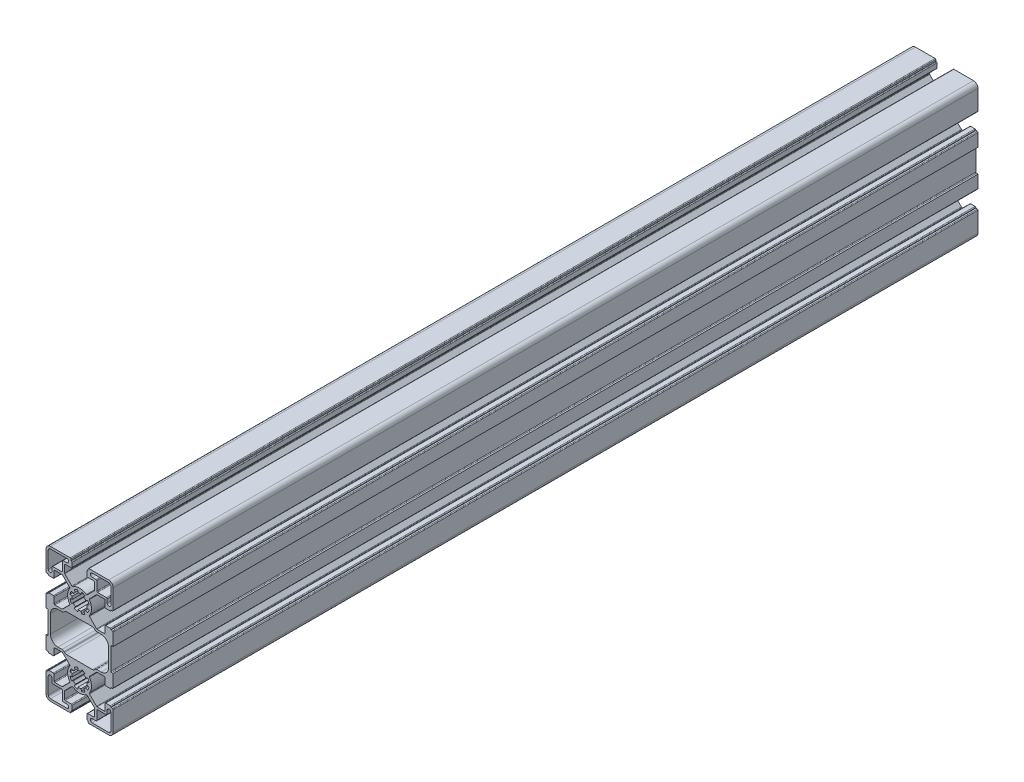
SolidWorks part; units mm, degrees
ref_plane "Front Plane" through (0, 0, 0) normal (0, 0, 1) x (1, 0, 0)
ref_plane "Top Plane" through (0, 0, 0) normal (0, 1, 0) x (1, 0, 0)
ref_plane "Right Plane" through (0, 0, 0) normal (1, 0, 0) x (0, 0, -1)
sketch "Sketch1" plane through (0, 0, 0) normal (0, 0, 1) x (1, 0, 0)
  line L0 (0, 45) -> (0, 0) construction
  line L1 (22.5, 22.5) -> (-22.5, 22.5) construction
  line L2 (-5.8, 45) -> (5.8, 45) construction
  line L3 (-5, 43.5) -> (5, 43.5) construction
  line L4 (-10.05, 32.55) -> (10.05, 32.55) construction
  line L5 (0, 22.5) -> (-10.05, 32.55) construction
  line L6 (0, 0) -> (0, -45) construction
  circle A0 centre (0, 22.5) radius 5 construction
  point P4 (0, 0)
  point P8 (0, 22.5)
  point P10 (0, 30.5)
  point P14 (0, 45)
  point P17 (0, 43.5)
  point P19 (0, 32.55)
  dimension "Center Hole Diameter" = 10
  dimension "T-Slot Depth" = 14.5
  dimension "T-Slot Width 2" = 11.6
  dimension "T-Slot Width" = 10
  dimension "Wall" = 1.5
  dimension "T-Slot Max Width" = 20.1
  dimension "Rail Width" = 45
  dimension "Rail Height" = 90
sketch "Sketch2" plane through (0, 0, 0) normal (1, 0, 0) x (0, 0, -1)
  line L0 (152.4, 0) -> (-152.4, 0) construction
  point P4 (0, 0)
  dimension "Length" = 304.8
sketch "Sketch3" plane through (0, 0, 0) normal (0, 0, 1) x (1, 0, 0)
  line L5 (-21, 31.0375) -> (-21, 42)
  line L9 (0, 22.5) -> (-22.5, 45) construction
  line L10 (-11.55, 12.45) -> (-6.3569, 17.6431)
  line L11 (-19.5, 43.5) -> (-8.5375, 43.5)
  line L38 (-5.8, 45) -> (-5.8, 43.5)
  line L46 (-5.8, 43.5) -> (-5, 43.5)
  line L62 (-5, 43.5) -> (-5, 39.525)
  line L74 (-5, 39.525) -> (-10.05, 39.525)
  line L76 (-10.05, 39.525) -> (-10.05, 34.05)
  line L77 (-10.05, 34.05) -> (-4.8569, 28.8569)
  line L78 (-18.525, 31.0375) -> (-18.525, 34.05)
  line L79 (-10.05, 39.525) -> (-10.05, 45) construction
  line L80 (0, 45) -> (0, 0) construction
  line L81 (-5.8, 45) -> (5.8, 45) construction
  line L82 (10.05, 34.05) -> (4.8569, 28.8569)
  line L83 (10.05, 39.525) -> (10.05, 34.05)
  line L84 (5, 39.525) -> (10.05, 39.525)
  line L85 (5, 43.5) -> (5, 39.525)
  line L86 (5.8, 43.5) -> (5, 43.5)
  line L87 (5.8, 45) -> (5.8, 43.5)
  line L88 (-22.5, 16.7) -> (-21, 16.7)
  line L89 (-21, 16.7) -> (-21, 17.5)
  line L90 (-21, 17.5) -> (-17.025, 17.5)
  line L91 (-17.025, 17.5) -> (-17.025, 12.45)
  line L92 (-17.025, 12.45) -> (-11.55, 12.45)
  line L93 (-11.55, 12.45) -> (-6.3569, 17.6431)
  line L94 (-11.55, 32.55) -> (-6.3569, 27.3569)
  line L95 (-17.025, 32.55) -> (-11.55, 32.55)
  line L96 (-17.025, 27.5) -> (-17.025, 32.55)
  line L97 (-21, 27.5) -> (-17.025, 27.5)
  line L98 (-21, 28.3) -> (-21, 27.5)
  line L99 (-22.5, 28.3) -> (-21, 28.3)
  line L100 (-22.5, 28.3) -> (-22.5, 42)
  line L101 (-19.5, 45) -> (-5.8, 45)
  line L102 (-18.525, 34.05) -> (-11.55, 34.05)
  line L103 (-8.5375, 41.025) -> (-11.55, 41.025)
  line L104 (-11.55, 41.025) -> (-11.55, 34.05)
  line L108 (-22.5, 0) -> (22.5, 0) construction
  line L113 (-21, 0) -> (-19.5, 0)
  line L117 (5.8, 45) -> (19.5, 45)
  line L118 (22.5, 42) -> (22.5, 28.3)
  line L120 (0, 22.5) -> (22.5, 22.5) construction
  line L121 (-22.5, 7.8) -> (-22.5, 16.7)
  line L136 (-22.5, 7.8) -> (-21, 7.8)
  line L137 (-21, 7.8) -> (-21, 0)
  line L138 (21, 7.8) -> (21, 0)
  line L139 (22.5, 7.8) -> (21, 7.8)
  line L140 (8.6003, 12.45) -> (-8.6003, 12.45)
  line L141 (-10.0145, 11.8642) -> (-10.3429, 11.5358)
  line L142 (-11.7571, 10.95) -> (-14.5, 10.95)
  line L143 (-19.5, 5.95) -> (-19.5, 0)
  line L144 (10.0145, 11.8642) -> (10.3429, 11.5358)
  line L145 (11.7571, 10.95) -> (14.5, 10.95)
  line L146 (19.5, 5.95) -> (19.5, 0)
  line L147 (22.5, 28.3) -> (21, 28.3)
  line L148 (21, 28.3) -> (21, 27.5)
  line L149 (21, 27.5) -> (17.025, 27.5)
  line L150 (17.025, 27.5) -> (17.025, 32.55)
  line L151 (17.025, 32.55) -> (11.55, 32.55)
  line L152 (11.55, 32.55) -> (6.3569, 27.3569)
  line L153 (11.55, 12.45) -> (6.3569, 17.6431)
  line L154 (17.025, 12.45) -> (11.55, 12.45)
  line L155 (17.025, 17.5) -> (17.025, 12.45)
  line L156 (21, 17.5) -> (17.025, 17.5)
  line L157 (21, 16.7) -> (21, 17.5)
  line L158 (22.5, 16.7) -> (21, 16.7)
  line L159 (11.55, 12.45) -> (6.3569, 17.6431)
  line L160 (22.5, 16.7) -> (22.5, 7.8)
  line L161 (8.5375, 43.5) -> (19.5, 43.5)
  line L162 (21, 42) -> (21, 31.0375)
  line L163 (8.5375, 41.025) -> (11.55, 41.025)
  line L164 (11.55, 41.025) -> (11.55, 34.05)
  line L165 (18.525, 31.0375) -> (18.525, 34.05)
  line L166 (18.525, 34.05) -> (11.55, 34.05)
  line L179 (0, 22.5) -> (-11.55, 34.05) construction
  line L180 (0, 22.5) -> (11.55, 34.05) construction
  line L181 (-18.525, 13.9625) -> (-18.525, 10.95) [skipped]
  line L182 (-21, 3) -> (-21, 13.9625) [skipped]
  line L183 (-8.5375, 1.5) -> (-19.5, 1.5) [skipped]
  line L184 (-8.5375, 3.975) -> (-11.55, 3.975) [skipped]
  line L185 (-11.55, 3.975) -> (-11.55, 10.95) [skipped]
  line L186 (-18.525, 10.95) -> (-11.55, 10.95) [skipped]
  line L187 (19.5, 1.5) -> (8.5375, 1.5) [skipped]
  line L188 (8.5375, 3.975) -> (11.55, 3.975) [skipped]
  line L189 (11.55, 3.975) -> (11.55, 10.95) [skipped]
  line L190 (18.525, 10.95) -> (11.55, 10.95) [skipped]
  line L191 (18.525, 13.9625) -> (18.525, 10.95) [skipped]
  line L192 (21, 13.9625) -> (21, 3) [skipped]
  line L193 (19.5, 0) -> (21, 0)
  arc A2 (-21, 42) -> (-19.5, 43.5) centre (-19.5, 42) cw
  arc A73 (-4.8569, 28.8569) -> (4.8569, 28.8569) centre (0, 22.5) cw
  arc A74 (-6.3569, 27.3569) -> (-6.3569, 17.6431) centre (0, 22.5) ccw
  arc A75 (-19.5, 45) -> (-22.5, 42) centre (-19.5, 42) ccw
  arc A76 (-21, 31.0375) -> (-18.525, 31.0375) centre (-19.7625, 31.0375) ccw
  arc A77 (-8.5375, 43.5) -> (-8.5375, 41.025) centre (-8.5375, 42.2625) cw
  arc A80 (19.5, 45) -> (22.5, 42) centre (19.5, 42) cw
  circle A88 centre (0, 22.5) radius 5 construction
  circle A89 centre (0, 22.5) radius 5
  arc A90 (-14.5, 10.95) -> (-19.5, 5.95) centre (-14.5, 5.95) ccw
  arc A91 (19.5, 43.5) -> (21, 42) centre (19.5, 42) cw
  arc A92 (6.3569, 27.3569) -> (6.3569, 17.6431) centre (0, 22.5) cw
  arc A93 (8.5375, 43.5) -> (8.5375, 41.025) centre (8.5375, 42.2625) ccw
  arc A94 (21, 31.0375) -> (18.525, 31.0375) centre (19.7625, 31.0375) cw
  arc A101 (-21, 13.9625) -> (-18.525, 13.9625) centre (-19.7625, 13.9625) cw [skipped]
  arc A102 (-19.5, 1.5) -> (-21, 3) centre (-19.5, 3) cw [skipped]
  arc A103 (-8.5375, 1.5) -> (-8.5375, 3.975) centre (-8.5375, 2.7375) ccw [skipped]
  arc A104 (8.5375, 1.5) -> (8.5375, 3.975) centre (8.5375, 2.7375) cw [skipped]
  arc A105 (21, 13.9625) -> (18.525, 13.9625) centre (19.7625, 13.9625) ccw [skipped]
  arc A106 (21, 3) -> (19.5, 1.5) centre (19.5, 3) cw [skipped]
  arc A107 (-8.6003, 12.45) -> (-10.0145, 11.8642) centre (-8.6003, 10.45) ccw
  arc A108 (-10.3429, 11.5358) -> (-11.7571, 10.95) centre (-11.7571, 12.95) cw
  arc A109 (8.6003, 12.45) -> (10.0145, 11.8642) centre (8.6003, 10.45) cw
  arc A110 (10.3429, 11.5358) -> (11.7571, 10.95) centre (11.7571, 12.95) ccw
  arc A111 (14.5, 10.95) -> (19.5, 5.95) centre (14.5, 5.95) cw
  point P54 (-14.2875, 32.55)
  point P111 (0, 12.45)
  dimension "D2" = 3
  dimension "D11" = 5
  dimension "D12" = 2
  dimension "D3" = 1.5
  dimension "D4" = 1.5
  dimension "D5" = 1.5
  dimension "D6" = 90
  dimension "D7" = 15.6
  dimension "D8" = 1.5
  dimension "D9" = 1.5
  dimension "D10" = 1.5
  dimension "D1" = 4
extrude "Boss-Extrude1" add sketch "Sketch3" along normal up to vertex (152.4 mm away) and the other way up to vertex (152.4 mm away) up to point (0, 0, 152.4) other way up to point (0, 0, -152.4)
fillet "Fillet1" radius 0.5 43 edges at (5, 43.5, 0) (5.8, 45, 0) (-5.8, 45, 0) (-5, 43.5, 0) (-10.05, 39.525, 0) (-5, 39.525, 0) (5, 39.525, 0) (-22.5, 16.7, 0) (-21, 17.5, 0) (-17.025, 17.5, 0) (-17.025, 12.45, 0) (-11.55, 12.45, 0) (-6.3569, 17.6431, 0) (-6.3569, 27.3569, 0) (-11.55, 32.55, 0) (-17.025, 32.55, 0) (-17.025, 27.5, 0) (-22.5, 28.3, 0) (-21, 27.5, 0) (-18.525, 34.05, 0) (-11.55, 34.05, 0) (-11.55, 41.025, 0) (4.8569, 28.8569, 0) (-4.8569, 28.8569, 0) (-10.05, 34.05, 0) (10.05, 39.525, 0) (10.05, 34.05, 0) (22.5, 16.7, 0) (21, 17.5, 0) (17.025, 17.5, 0) (17.025, 12.45, 0) (6.3569, 27.3569, 0) (11.55, 32.55, 0) (22.5, 28.3, 0) (21, 27.5, 0) (17.025, 27.5, 0) (11.55, 41.025, 0) (18.525, 34.05, 0) (11.55, 34.05, 0) (11.55, 12.45, 0) (6.3569, 17.6431, 0) (21, 7.8, 0) (-21, 7.8, 0)
sketch "Sketch4" plane through (0, 0, 152.4) normal (0, 0, 1) x (1, 0, 0)
  line L0 (-1.2681, 28.8751) -> (-0.9755, 27.4039)
  line L1 (0, 22.5) -> (0, 8) construction
  line L2 (-3.6112, 27.9046) -> (-2.7779, 26.6573)
  line L3 (1.2681, 28.8751) -> (0.9755, 27.4039)
  line L4 (3.6112, 27.9046) -> (2.7779, 26.6573)
  line L5 (5.4046, 26.1112) -> (4.1573, 25.2779)
  line L6 (6.3751, 23.7681) -> (4.9039, 23.4755)
  line L7 (6.3751, 21.2319) -> (4.9039, 21.5245)
  line L8 (5.4046, 18.8888) -> (4.1573, 19.7221)
  line L9 (3.6112, 17.0954) -> (2.7779, 18.3427)
  line L10 (1.2681, 16.1249) -> (0.9755, 17.5961)
  line L11 (-1.2681, 16.1249) -> (-0.9755, 17.5961)
  line L12 (-3.6112, 17.0954) -> (-2.7779, 18.3427)
  line L13 (-5.4046, 18.8888) -> (-4.1573, 19.7221)
  line L14 (-6.3751, 21.2319) -> (-4.9039, 21.5245)
  line L15 (-6.3751, 23.7681) -> (-4.9039, 23.4755)
  line L16 (-5.4046, 26.1112) -> (-4.1573, 25.2779)
  line L17 (0, 22.5) -> (-0.9755, 27.4039) construction
  line L18 (0, 22.5) -> (2.7779, 26.6573) construction
  arc A0 (-1.2681, 28.8751) -> (-3.6112, 27.9046) centre (0, 22.5) ccw
  circle A1 centre (0, 22.5) radius 5 construction
  arc A2 (-0.9755, 27.4039) -> (-2.7779, 26.6573) centre (0, 22.5) ccw
  arc A4 (2.7779, 26.6573) -> (0.9755, 27.4039) centre (0, 22.5) ccw
  arc A5 (3.6112, 27.9046) -> (1.2681, 28.8751) centre (0, 22.5) ccw
  arc A6 (4.9039, 23.4755) -> (4.1573, 25.2779) centre (0, 22.5) ccw
  arc A7 (6.3751, 23.7681) -> (5.4046, 26.1112) centre (0, 22.5) ccw
  arc A8 (4.1573, 19.7221) -> (4.9039, 21.5245) centre (0, 22.5) ccw
  arc A9 (5.4046, 18.8888) -> (6.3751, 21.2319) centre (0, 22.5) ccw
  arc A10 (0.9755, 17.5961) -> (2.7779, 18.3427) centre (0, 22.5) ccw
  arc A11 (1.2681, 16.1249) -> (3.6112, 17.0954) centre (0, 22.5) ccw
  arc A12 (-2.7779, 18.3427) -> (-0.9755, 17.5961) centre (0, 22.5) ccw
  arc A13 (-3.6112, 17.0954) -> (-1.2681, 16.1249) centre (0, 22.5) ccw
  arc A14 (-4.9039, 21.5245) -> (-4.1573, 19.7221) centre (0, 22.5) ccw
  arc A15 (-6.3751, 21.2319) -> (-5.4046, 18.8888) centre (0, 22.5) ccw
  arc A16 (-4.1573, 25.2779) -> (-4.9039, 23.4755) centre (0, 22.5) ccw
  arc A17 (-5.4046, 26.1112) -> (-6.3751, 23.7681) centre (0, 22.5) ccw
  dimension "D1" = 1.5
  dimension "D2" = 22.5
  dimension "D5" = 45
  dimension "D4" = 8
extrude "Cut-Extrude1" cut sketch "Sketch4" against normal through all
mirror "Mirror1" about plane through (0, 0, 0) normal (0, 1, 0) of "Cut-Extrude1", "Fillet1", "Boss-Extrude1"
sketch "Sketch5" plane through (0, 0, 152.4) normal (0, 0, 1) x (1, 0, 0)
  line L6 (-18.525, -33.55) -> (-18.525, -31.0375)
  line L7 (-12.05, -34.05) -> (-18.025, -34.05)
  line L8 (-11.55, -40.525) -> (-11.55, -34.55)
  line L9 (-8.5375, -41.025) -> (-11.05, -41.025)
  line L10 (-19.5, -43.5) -> (-8.5375, -43.5)
  line L11 (-21, -31.0375) -> (-21, -42)
  line L12 (-18.525, -33.55) -> (-18.525, -31.0375)
  line L13 (-12.05, -34.05) -> (-18.025, -34.05)
  line L14 (-11.55, -40.525) -> (-11.55, -34.55)
  line L15 (-8.5375, -41.025) -> (-11.05, -41.025)
  line L16 (-19.5, -43.5) -> (-8.5375, -43.5)
  line L17 (-21, -31.0375) -> (-21, -42)
  line L18 (11.05, -41.025) -> (8.5375, -41.025)
  line L19 (11.55, -34.55) -> (11.55, -40.525)
  line L20 (18.025, -34.05) -> (12.05, -34.05)
  line L21 (18.525, -31.0375) -> (18.525, -33.55)
  line L22 (21, -42) -> (21, -31.0375)
  line L23 (8.5375, -43.5) -> (19.5, -43.5)
  line L24 (11.05, -41.025) -> (8.5375, -41.025)
  line L25 (11.55, -34.55) -> (11.55, -40.525)
  line L26 (18.025, -34.05) -> (12.05, -34.05)
  line L27 (18.525, -31.0375) -> (18.525, -33.55)
  line L28 (21, -42) -> (21, -31.0375)
  line L29 (8.5375, -43.5) -> (19.5, -43.5)
  line L30 (11.55, 40.525) -> (11.55, 34.55)
  line L31 (8.5375, 41.025) -> (11.05, 41.025)
  line L32 (19.5, 43.5) -> (8.5375, 43.5)
  line L33 (21, 31.0375) -> (21, 42)
  line L34 (18.525, 33.55) -> (18.525, 31.0375)
  line L35 (12.05, 34.05) -> (18.025, 34.05)
  line L36 (-19.5, 5.95) -> (-19.5, -5.95)
  line L37 (-11.7571, 10.95) -> (-14.5, 10.95)
  line L38 (-10.0145, 11.8642) -> (-10.3429, 11.5358)
  line L39 (8.6003, 12.45) -> (-8.6003, 12.45)
  line L40 (-2.7779, -26.6573) -> (-3.6112, -27.9046)
  line L41 (-5.4046, -26.1112) -> (-4.1573, -25.2779)
  line L42 (-4.9039, -23.4755) -> (-6.3751, -23.7681)
  line L43 (-6.3751, -21.2319) -> (-4.9039, -21.5245)
  line L44 (-4.1573, -19.7221) -> (-5.4046, -18.8888)
  line L45 (-3.6112, -17.0954) -> (-2.7779, -18.3427)
  line L46 (-0.9755, -17.5961) -> (-1.2681, -16.1249)
  line L47 (1.2681, -16.1249) -> (0.9755, -17.5961)
  line L48 (2.7779, -18.3427) -> (3.6112, -17.0954)
  line L49 (5.4046, -18.8888) -> (4.1573, -19.7221)
  line L50 (4.9039, -21.5245) -> (6.3751, -21.2319)
  line L51 (6.3751, -23.7681) -> (4.9039, -23.4755)
  line L52 (4.1573, -25.2779) -> (5.4046, -26.1112)
  line L53 (3.6112, -27.9046) -> (2.7779, -26.6573)
  line L54 (0.9755, -27.4039) -> (1.2681, -28.8751)
  line L55 (-1.2681, -28.8751) -> (-0.9755, -27.4039)
  line L56 (-2.7779, -26.6573) -> (-3.6112, -27.9046)
  line L57 (-5.4046, -26.1112) -> (-4.1573, -25.2779)
  line L58 (-4.9039, -23.4755) -> (-6.3751, -23.7681)
  line L59 (-6.3751, -21.2319) -> (-4.9039, -21.5245)
  line L60 (-4.1573, -19.7221) -> (-5.4046, -18.8888)
  line L61 (-3.6112, -17.0954) -> (-2.7779, -18.3427)
  line L62 (-0.9755, -17.5961) -> (-1.2681, -16.1249)
  line L63 (1.2681, -16.1249) -> (0.9755, -17.5961)
  line L64 (2.7779, -18.3427) -> (3.6112, -17.0954)
  line L65 (5.4046, -18.8888) -> (4.1573, -19.7221)
  line L66 (4.9039, -21.5245) -> (6.3751, -21.2319)
  line L67 (6.3751, -23.7681) -> (4.9039, -23.4755)
  line L68 (4.1573, -25.2779) -> (5.4046, -26.1112)
  line L69 (3.6112, -27.9046) -> (2.7779, -26.6573)
  line L70 (0.9755, -27.4039) -> (1.2681, -28.8751)
  line L71 (-1.2681, -28.8751) -> (-0.9755, -27.4039)
  line L72 (10.3429, 11.5358) -> (10.0145, 11.8642)
  line L73 (14.5, 10.95) -> (11.7571, 10.95)
  line L74 (19.5, -5.95) -> (19.5, 5.95)
  line L75 (11.7571, -10.95) -> (14.5, -10.95)
  line L76 (10.0145, -11.8642) -> (10.3429, -11.5358)
  line L77 (-8.6003, -12.45) -> (8.6003, -12.45)
  line L78 (-10.3429, -11.5358) -> (-10.0145, -11.8642)
  line L79 (-14.5, -10.95) -> (-11.7571, -10.95)
  line L80 (-19.5, 5.95) -> (-19.5, -5.95)
  line L81 (-11.7571, 10.95) -> (-14.5, 10.95)
  line L82 (-10.0145, 11.8642) -> (-10.3429, 11.5358)
  line L83 (8.6003, 12.45) -> (-8.6003, 12.45)
  line L84 (10.3429, 11.5358) -> (10.0145, 11.8642)
  line L85 (14.5, 10.95) -> (11.7571, 10.95)
  line L86 (19.5, -5.95) -> (19.5, 5.95)
  line L87 (11.7571, -10.95) -> (14.5, -10.95)
  line L88 (10.0145, -11.8642) -> (10.3429, -11.5358)
  line L89 (-8.6003, -12.45) -> (8.6003, -12.45)
  line L90 (21, -16.7) -> (22, -16.7)
  line L91 (22.5, -16.2) -> (22.5, -7.8)
  line L92 (22.5, -7.8) -> (21.5, -7.8)
  line L93 (21, -7.3) -> (21, 7.3)
  line L94 (21.5, 7.8) -> (22.5, 7.8)
  line L95 (22.5, 7.8) -> (22.5, 16.2)
  line L96 (22, 16.7) -> (21, 16.7)
  line L97 (21, 16.7) -> (21, 17)
  line L98 (20.5, 17.5) -> (17.525, 17.5)
  line L99 (17.025, 17) -> (17.025, 12.95)
  line L100 (16.525, 12.45) -> (11.7571, 12.45)
  line L101 (11.4036, 12.5964) -> (6.6582, 17.3418)
  line L102 (6.6582, 27.6582) -> (11.4036, 32.4036)
  line L103 (11.7571, 32.55) -> (17.025, 32.55)
  line L104 (17.025, 32.55) -> (17.025, 28)
  line L105 (17.525, 27.5) -> (20.5, 27.5)
  line L106 (21, 28) -> (21, 28.3)
  line L107 (21, 28.3) -> (22, 28.3)
  line L108 (22.5, 28.8) -> (22.5, 42)
  line L109 (19.5, 45) -> (6.3, 45)
  line L110 (5.8, 44.5) -> (5.8, 43.5)
  line L111 (5.8, 43.5) -> (5.5, 43.5)
  line L112 (5, 43) -> (5, 40.025)
  line L113 (5.5, 39.525) -> (9.55, 39.525)
  line L114 (10.05, 39.025) -> (10.05, 34.2571)
  line L115 (9.9036, 33.9036) -> (5.1582, 29.1582)
  line L116 (-5.1582, 29.1582) -> (-9.9036, 33.9036)
  line L117 (-10.05, 34.2571) -> (-10.05, 39.025)
  line L118 (-9.55, 39.525) -> (-5.5, 39.525)
  line L119 (-5, 40.025) -> (-5, 43)
  line L120 (-5.5, 43.5) -> (-5.8, 43.5)
  line L121 (-5.8, 43.5) -> (-5.8, 44.5)
  line L122 (-6.3, 45) -> (-19.5, 45)
  line L123 (-22.5, 42) -> (-22.5, 28.8)
  line L124 (-22, 28.3) -> (-21, 28.3)
  line L125 (-21, 28.3) -> (-21, 28)
  line L126 (-20.5, 27.5) -> (-17.525, 27.5)
  line L127 (-17.025, 28) -> (-17.025, 32.05)
  line L128 (-16.525, 32.55) -> (-11.7571, 32.55)
  line L129 (-11.4036, 32.4036) -> (-6.6582, 27.6582)
  line L130 (-6.6582, 17.3418) -> (-11.4036, 12.5964)
  line L131 (-11.7571, 12.45) -> (-16.525, 12.45)
  line L132 (-17.025, 12.95) -> (-17.025, 17)
  line L133 (-17.525, 17.5) -> (-20.5, 17.5)
  line L134 (-21, 17) -> (-21, 16.7)
  line L135 (-21, 16.7) -> (-22, 16.7)
  line L136 (-22.5, 16.2) -> (-22.5, 7.8)
  line L137 (-22.5, 7.8) -> (-21.5, 7.8)
  line L138 (-21, 7.3) -> (-21, -7.3)
  line L139 (-21.5, -7.8) -> (-22.5, -7.8)
  line L140 (-22.5, -7.8) -> (-22.5, -16.2)
  line L141 (-22, -16.7) -> (-21, -16.7)
  line L142 (-21, -16.7) -> (-21, -17)
  line L143 (-20.5, -17.5) -> (-17.525, -17.5)
  line L144 (-17.025, -17) -> (-17.025, -12.95)
  line L145 (-16.525, -12.45) -> (-11.7571, -12.45)
  line L146 (-11.4036, -12.5964) -> (-6.6582, -17.3418)
  line L147 (-6.6582, -27.6582) -> (-11.4036, -32.4036)
  line L148 (-11.7571, -32.55) -> (-16.525, -32.55)
  line L149 (-17.025, -32.05) -> (-17.025, -28)
  line L150 (-17.525, -27.5) -> (-20.5, -27.5)
  line L151 (-21, -28) -> (-21, -28.3)
  line L152 (-21, -28.3) -> (-22, -28.3)
  line L153 (-22.5, -28.8) -> (-22.5, -42)
  line L154 (-19.5, -45) -> (-6.3, -45)
  line L155 (-5.8, -44.5) -> (-5.8, -43.5)
  line L156 (-5.8, -43.5) -> (-5.5, -43.5)
  line L157 (-5, -43) -> (-5, -40.025)
  line L158 (-5.5, -39.525) -> (-9.55, -39.525)
  line L159 (-10.05, -39.025) -> (-10.05, -34.2571)
  line L160 (-9.9036, -33.9036) -> (-5.1582, -29.1582)
  line L161 (5.1582, -29.1582) -> (9.9036, -33.9036)
  line L162 (10.05, -34.2571) -> (10.05, -39.025)
  line L163 (9.55, -39.525) -> (5.5, -39.525)
  line L164 (5, -40.025) -> (5, -43)
  line L165 (5.5, -43.5) -> (5.8, -43.5)
  line L166 (5.8, -43.5) -> (5.8, -44.5)
  line L167 (6.3, -45) -> (19.5, -45)
  line L168 (22.5, -42) -> (22.5, -28.8)
  line L169 (22, -28.3) -> (21, -28.3)
  line L170 (21, -28.3) -> (21, -28)
  line L171 (20.5, -27.5) -> (17.525, -27.5)
  line L172 (17.025, -28) -> (17.025, -32.55)
  line L173 (17.025, -32.55) -> (11.7571, -32.55)
  line L174 (11.4036, -32.4036) -> (6.6582, -27.6582)
  line L175 (6.6582, -17.3418) -> (11.4036, -12.5964)
  line L176 (11.7571, -12.45) -> (16.525, -12.45)
  line L177 (17.025, -12.95) -> (17.025, -17)
  line L178 (17.525, -17.5) -> (20.5, -17.5)
  line L179 (21, -17) -> (21, -16.7)
  line L180 (21, -16.7) -> (22, -16.7)
  line L181 (22.5, -16.2) -> (22.5, -7.8)
  line L182 (22.5, -7.8) -> (21.5, -7.8)
  line L183 (21, -7.3) -> (21, 7.3)
  line L184 (21.5, 7.8) -> (22.5, 7.8)
  line L185 (22.5, 7.8) -> (22.5, 16.2)
  line L186 (22, 16.7) -> (21, 16.7)
  line L187 (21, 16.7) -> (21, 17)
  line L188 (20.5, 17.5) -> (17.525, 17.5)
  line L189 (17.025, 17) -> (17.025, 12.95)
  line L190 (16.525, 12.45) -> (11.7571, 12.45)
  line L191 (11.4036, 12.5964) -> (6.6582, 17.3418)
  line L192 (6.6582, 27.6582) -> (11.4036, 32.4036)
  line L193 (11.7571, 32.55) -> (17.025, 32.55)
  line L194 (17.025, 32.55) -> (17.025, 28)
  line L195 (17.525, 27.5) -> (20.5, 27.5)
  line L196 (21, 28) -> (21, 28.3)
  line L197 (21, 28.3) -> (22, 28.3)
  line L198 (22.5, 28.8) -> (22.5, 42)
  line L199 (19.5, 45) -> (6.3, 45)
  line L200 (5.8, 44.5) -> (5.8, 43.5)
  line L201 (5.8, 43.5) -> (5.5, 43.5)
  line L202 (5, 43) -> (5, 40.025)
  line L203 (5.5, 39.525) -> (9.55, 39.525)
  line L204 (10.05, 39.025) -> (10.05, 34.2571)
  line L205 (9.9036, 33.9036) -> (5.1582, 29.1582)
  line L206 (-5.1582, 29.1582) -> (-9.9036, 33.9036)
  line L207 (-10.05, 34.2571) -> (-10.05, 39.025)
  line L208 (-9.55, 39.525) -> (-5.5, 39.525)
  line L209 (-5, 40.025) -> (-5, 43)
  line L210 (-5.5, 43.5) -> (-5.8, 43.5)
  line L211 (-5.8, 43.5) -> (-5.8, 44.5)
  line L212 (-6.3, 45) -> (-19.5, 45)
  line L213 (-22.5, 42) -> (-22.5, 28.8)
  line L214 (-22, 28.3) -> (-21, 28.3)
  line L215 (-21, 28.3) -> (-21, 28)
  line L216 (-20.5, 27.5) -> (-17.525, 27.5)
  line L217 (-17.025, 28) -> (-17.025, 32.05)
  line L218 (-16.525, 32.55) -> (-11.7571, 32.55)
  line L219 (-11.4036, 32.4036) -> (-6.6582, 27.6582)
  line L220 (-6.6582, 17.3418) -> (-11.4036, 12.5964)
  line L221 (-11.7571, 12.45) -> (-16.525, 12.45)
  line L222 (-17.025, 12.95) -> (-17.025, 17)
  line L223 (-17.525, 17.5) -> (-20.5, 17.5)
  line L224 (-21, 17) -> (-21, 16.7)
  line L225 (-21, 16.7) -> (-22, 16.7)
  line L226 (-22.5, 16.2) -> (-22.5, 7.8)
  line L227 (-22.5, 7.8) -> (-21.5, 7.8)
  line L228 (-21, 7.3) -> (-21, -7.3)
  line L229 (-21.5, -7.8) -> (-22.5, -7.8)
  line L230 (-22.5, -7.8) -> (-22.5, -16.2)
  line L231 (-22, -16.7) -> (-21, -16.7)
  line L232 (-21, -16.7) -> (-21, -17)
  line L233 (-20.5, -17.5) -> (-17.525, -17.5)
  line L234 (-17.025, -17) -> (-17.025, -12.95)
  line L235 (-16.525, -12.45) -> (-11.7571, -12.45)
  line L236 (-11.4036, -12.5964) -> (-6.6582, -17.3418)
  line L237 (-6.6582, -27.6582) -> (-11.4036, -32.4036)
  line L238 (-11.7571, -32.55) -> (-16.525, -32.55)
  line L239 (-17.025, -32.05) -> (-17.025, -28)
  line L240 (-17.525, -27.5) -> (-20.5, -27.5)
  line L241 (-21, -28) -> (-21, -28.3)
  line L242 (-21, -28.3) -> (-22, -28.3)
  line L243 (-22.5, -28.8) -> (-22.5, -42)
  line L244 (-19.5, -45) -> (-6.3, -45)
  line L245 (-5.8, -44.5) -> (-5.8, -43.5)
  line L246 (-5.8, -43.5) -> (-5.5, -43.5)
  line L247 (-5, -43) -> (-5, -40.025)
  line L248 (-5.5, -39.525) -> (-9.55, -39.525)
  line L249 (-10.05, -39.025) -> (-10.05, -34.2571)
  line L250 (-9.9036, -33.9036) -> (-5.1582, -29.1582)
  line L251 (5.1582, -29.1582) -> (9.9036, -33.9036)
  line L252 (10.05, -34.2571) -> (10.05, -39.025)
  line L253 (9.55, -39.525) -> (5.5, -39.525)
  line L254 (5, -40.025) -> (5, -43)
  line L255 (5.5, -43.5) -> (5.8, -43.5)
  line L256 (5.8, -43.5) -> (5.8, -44.5)
  line L257 (6.3, -45) -> (19.5, -45)
  line L258 (22.5, -42) -> (22.5, -28.8)
  line L259 (22, -28.3) -> (21, -28.3)
  line L260 (21, -28.3) -> (21, -28)
  line L261 (20.5, -27.5) -> (17.525, -27.5)
  line L262 (17.025, -28) -> (17.025, -32.55)
  line L263 (17.025, -32.55) -> (11.7571, -32.55)
  line L264 (11.4036, -32.4036) -> (6.6582, -27.6582)
  line L265 (6.6582, -17.3418) -> (11.4036, -12.5964)
  line L266 (11.7571, -12.45) -> (16.525, -12.45)
  line L267 (17.025, -12.95) -> (17.025, -17)
  line L268 (17.525, -17.5) -> (20.5, -17.5)
  line L269 (21, -17) -> (21, -16.7)
  line L270 (-10.3429, -11.5358) -> (-10.0145, -11.8642)
  line L271 (-14.5, -10.95) -> (-11.7571, -10.95)
  line L272 (11.55, 40.525) -> (11.55, 34.55)
  line L273 (8.5375, 41.025) -> (11.05, 41.025)
  line L274 (19.5, 43.5) -> (8.5375, 43.5)
  line L275 (21, 31.0375) -> (21, 42)
  line L276 (-0.9755, 27.4039) -> (-1.2681, 28.8751)
  line L277 (1.2681, 28.8751) -> (0.9755, 27.4039)
  line L278 (2.7779, 26.6573) -> (3.6112, 27.9046)
  line L279 (5.4046, 26.1112) -> (4.1573, 25.2779)
  line L280 (4.9039, 23.4755) -> (6.3751, 23.7681)
  line L281 (6.3751, 21.2319) -> (4.9039, 21.5245)
  line L282 (4.1573, 19.7221) -> (5.4046, 18.8888)
  line L283 (3.6112, 17.0954) -> (2.7779, 18.3427)
  line L284 (0.9755, 17.5961) -> (1.2681, 16.1249)
  line L285 (-1.2681, 16.1249) -> (-0.9755, 17.5961)
  line L286 (-2.7779, 18.3427) -> (-3.6112, 17.0954)
  line L287 (-5.4046, 18.8888) -> (-4.1573, 19.7221)
  line L288 (-4.9039, 21.5245) -> (-6.3751, 21.2319)
  line L289 (-6.3751, 23.7681) -> (-4.9039, 23.4755)
  line L290 (-4.1573, 25.2779) -> (-5.4046, 26.1112)
  line L291 (-3.6112, 27.9046) -> (-2.7779, 26.6573)
  line L292 (-0.9755, 27.4039) -> (-1.2681, 28.8751)
  line L293 (1.2681, 28.8751) -> (0.9755, 27.4039)
  line L294 (2.7779, 26.6573) -> (3.6112, 27.9046)
  line L295 (5.4046, 26.1112) -> (4.1573, 25.2779)
  line L296 (4.9039, 23.4755) -> (6.3751, 23.7681)
  line L297 (6.3751, 21.2319) -> (4.9039, 21.5245)
  line L298 (4.1573, 19.7221) -> (5.4046, 18.8888)
  line L299 (3.6112, 17.0954) -> (2.7779, 18.3427)
  line L300 (0.9755, 17.5961) -> (1.2681, 16.1249)
  line L301 (-1.2681, 16.1249) -> (-0.9755, 17.5961)
  line L302 (-2.7779, 18.3427) -> (-3.6112, 17.0954)
  line L303 (-5.4046, 18.8888) -> (-4.1573, 19.7221)
  line L304 (-4.9039, 21.5245) -> (-6.3751, 21.2319)
  line L305 (-6.3751, 23.7681) -> (-4.9039, 23.4755)
  line L306 (-4.1573, 25.2779) -> (-5.4046, 26.1112)
  line L307 (-3.6112, 27.9046) -> (-2.7779, 26.6573)
  line L308 (18.525, 33.55) -> (18.525, 31.0375)
  line L309 (12.05, 34.05) -> (18.025, 34.05)
  line L310 (-18.025, 34.05) -> (-12.05, 34.05)
  line L311 (-18.525, 31.0375) -> (-18.525, 33.55)
  line L312 (-21, 42) -> (-21, 31.0375)
  line L313 (-8.5375, 43.5) -> (-19.5, 43.5)
  line L314 (-11.05, 41.025) -> (-8.5375, 41.025)
  line L315 (-11.55, 34.55) -> (-11.55, 40.525)
  line L316 (-18.025, 34.05) -> (-12.05, 34.05)
  line L317 (-18.525, 31.0375) -> (-18.525, 33.55)
  line L318 (-21, 42) -> (-21, 31.0375)
  line L319 (-8.5375, 43.5) -> (-19.5, 43.5)
  line L320 (-11.05, 41.025) -> (-8.5375, 41.025)
  line L321 (-11.55, 34.55) -> (-11.55, 40.525)
  arc A6 (-18.525, -33.55) -> (-18.025, -34.05) centre (-18.025, -33.55) ccw
  arc A7 (-11.55, -34.55) -> (-12.05, -34.05) centre (-12.05, -34.55) ccw
  arc A8 (-11.55, -40.525) -> (-11.05, -41.025) centre (-11.05, -40.525) ccw
  arc A9 (-8.5375, -43.5) -> (-8.5375, -41.025) centre (-8.5375, -42.2625) ccw
  arc A10 (-21, -42) -> (-19.5, -43.5) centre (-19.5, -42) ccw
  arc A11 (-18.525, -31.0375) -> (-21, -31.0375) centre (-19.7625, -31.0375) ccw
  arc A12 (-18.525, -33.55) -> (-18.025, -34.05) centre (-18.025, -33.55) ccw
  arc A13 (-11.55, -34.55) -> (-12.05, -34.05) centre (-12.05, -34.55) ccw
  arc A14 (-11.55, -40.525) -> (-11.05, -41.025) centre (-11.05, -40.525) ccw
  arc A15 (-8.5375, -43.5) -> (-8.5375, -41.025) centre (-8.5375, -42.2625) ccw
  arc A16 (-21, -42) -> (-19.5, -43.5) centre (-19.5, -42) ccw
  arc A17 (-18.525, -31.0375) -> (-21, -31.0375) centre (-19.7625, -31.0375) ccw
  arc A18 (11.05, -41.025) -> (11.55, -40.525) centre (11.05, -40.525) ccw
  arc A19 (12.05, -34.05) -> (11.55, -34.55) centre (12.05, -34.55) ccw
  arc A20 (18.025, -34.05) -> (18.525, -33.55) centre (18.025, -33.55) ccw
  arc A21 (21, -31.0375) -> (18.525, -31.0375) centre (19.7625, -31.0375) ccw
  arc A22 (19.5, -43.5) -> (21, -42) centre (19.5, -42) ccw
  arc A23 (8.5375, -41.025) -> (8.5375, -43.5) centre (8.5375, -42.2625) ccw
  arc A24 (11.05, -41.025) -> (11.55, -40.525) centre (11.05, -40.525) ccw
  arc A25 (12.05, -34.05) -> (11.55, -34.55) centre (12.05, -34.55) ccw
  arc A26 (18.025, -34.05) -> (18.525, -33.55) centre (18.025, -33.55) ccw
  arc A27 (21, -31.0375) -> (18.525, -31.0375) centre (19.7625, -31.0375) ccw
  arc A28 (19.5, -43.5) -> (21, -42) centre (19.5, -42) ccw
  arc A29 (8.5375, -41.025) -> (8.5375, -43.5) centre (8.5375, -42.2625) ccw
  arc A30 (11.55, 40.525) -> (11.05, 41.025) centre (11.05, 40.525) ccw
  arc A31 (8.5375, 43.5) -> (8.5375, 41.025) centre (8.5375, 42.2625) ccw
  arc A32 (21, 42) -> (19.5, 43.5) centre (19.5, 42) ccw
  arc A33 (18.525, 31.0375) -> (21, 31.0375) centre (19.7625, 31.0375) ccw
  arc A34 (18.525, 33.55) -> (18.025, 34.05) centre (18.025, 33.55) ccw
  arc A35 (11.55, 34.55) -> (12.05, 34.05) centre (12.05, 34.55) ccw
  arc A36 (-19.5, -5.95) -> (-14.5, -10.95) centre (-14.5, -5.95) ccw
  arc A37 (-14.5, 10.95) -> (-19.5, 5.95) centre (-14.5, 5.95) ccw
  arc A38 (-11.7571, 10.95) -> (-10.3429, 11.5358) centre (-11.7571, 12.95) ccw
  arc A39 (-8.6003, 12.45) -> (-10.0145, 11.8642) centre (-8.6003, 10.45) ccw
  arc A40 (-3.6112, -27.9046) -> (-1.2681, -28.8751) centre (0, -22.5) ccw
  arc A41 (-4.1573, -25.2779) -> (-2.7779, -26.6573) centre (0, -22.5) ccw
  arc A42 (-6.3751, -23.7681) -> (-5.4046, -26.1112) centre (0, -22.5) ccw
  arc A43 (-4.9039, -21.5245) -> (-4.9039, -23.4755) centre (0, -22.5) ccw
  arc A44 (-5.4046, -18.8888) -> (-6.3751, -21.2319) centre (0, -22.5) ccw
  arc A45 (-2.7779, -18.3427) -> (-4.1573, -19.7221) centre (0, -22.5) ccw
  arc A46 (-1.2681, -16.1249) -> (-3.6112, -17.0954) centre (0, -22.5) ccw
  arc A47 (0.9755, -17.5961) -> (-0.9755, -17.5961) centre (0, -22.5) ccw
  arc A48 (3.6112, -17.0954) -> (1.2681, -16.1249) centre (0, -22.5) ccw
  arc A49 (4.1573, -19.7221) -> (2.7779, -18.3427) centre (0, -22.5) ccw
  arc A50 (6.3751, -21.2319) -> (5.4046, -18.8888) centre (0, -22.5) ccw
  arc A51 (4.9039, -23.4755) -> (4.9039, -21.5245) centre (0, -22.5) ccw
  arc A52 (5.4046, -26.1112) -> (6.3751, -23.7681) centre (0, -22.5) ccw
  arc A53 (2.7779, -26.6573) -> (4.1573, -25.2779) centre (0, -22.5) ccw
  arc A54 (1.2681, -28.8751) -> (3.6112, -27.9046) centre (0, -22.5) ccw
  arc A55 (-0.9755, -27.4039) -> (0.9755, -27.4039) centre (0, -22.5) ccw
  arc A56 (-3.6112, -27.9046) -> (-1.2681, -28.8751) centre (0, -22.5) ccw
  arc A57 (-4.1573, -25.2779) -> (-2.7779, -26.6573) centre (0, -22.5) ccw
  arc A58 (-6.3751, -23.7681) -> (-5.4046, -26.1112) centre (0, -22.5) ccw
  arc A59 (-4.9039, -21.5245) -> (-4.9039, -23.4755) centre (0, -22.5) ccw
  arc A60 (-5.4046, -18.8888) -> (-6.3751, -21.2319) centre (0, -22.5) ccw
  arc A61 (-2.7779, -18.3427) -> (-4.1573, -19.7221) centre (0, -22.5) ccw
  arc A62 (-1.2681, -16.1249) -> (-3.6112, -17.0954) centre (0, -22.5) ccw
  arc A63 (0.9755, -17.5961) -> (-0.9755, -17.5961) centre (0, -22.5) ccw
  arc A64 (3.6112, -17.0954) -> (1.2681, -16.1249) centre (0, -22.5) ccw
  arc A65 (4.1573, -19.7221) -> (2.7779, -18.3427) centre (0, -22.5) ccw
  arc A66 (6.3751, -21.2319) -> (5.4046, -18.8888) centre (0, -22.5) ccw
  arc A67 (4.9039, -23.4755) -> (4.9039, -21.5245) centre (0, -22.5) ccw
  arc A68 (5.4046, -26.1112) -> (6.3751, -23.7681) centre (0, -22.5) ccw
  arc A69 (2.7779, -26.6573) -> (4.1573, -25.2779) centre (0, -22.5) ccw
  arc A70 (1.2681, -28.8751) -> (3.6112, -27.9046) centre (0, -22.5) ccw
  arc A71 (-0.9755, -27.4039) -> (0.9755, -27.4039) centre (0, -22.5) ccw
  arc A72 (10.0145, 11.8642) -> (8.6003, 12.45) centre (8.6003, 10.45) ccw
  arc A73 (10.3429, 11.5358) -> (11.7571, 10.95) centre (11.7571, 12.95) ccw
  arc A74 (19.5, 5.95) -> (14.5, 10.95) centre (14.5, 5.95) ccw
  arc A75 (14.5, -10.95) -> (19.5, -5.95) centre (14.5, -5.95) ccw
  arc A76 (11.7571, -10.95) -> (10.3429, -11.5358) centre (11.7571, -12.95) ccw
  arc A77 (8.6003, -12.45) -> (10.0145, -11.8642) centre (8.6003, -10.45) ccw
  arc A78 (-10.0145, -11.8642) -> (-8.6003, -12.45) centre (-8.6003, -10.45) ccw
  arc A79 (-10.3429, -11.5358) -> (-11.7571, -10.95) centre (-11.7571, -12.95) ccw
  arc A80 (-19.5, -5.95) -> (-14.5, -10.95) centre (-14.5, -5.95) ccw
  arc A81 (-14.5, 10.95) -> (-19.5, 5.95) centre (-14.5, 5.95) ccw
  arc A82 (-11.7571, 10.95) -> (-10.3429, 11.5358) centre (-11.7571, 12.95) ccw
  arc A83 (-8.6003, 12.45) -> (-10.0145, 11.8642) centre (-8.6003, 10.45) ccw
  arc A84 (22, -16.7) -> (22.5, -16.2) centre (22, -16.2) ccw
  arc A85 (21, -7.3) -> (21.5, -7.8) centre (21.5, -7.3) ccw
  arc A86 (21.5, 7.8) -> (21, 7.3) centre (21.5, 7.3) ccw
  arc A87 (22.5, 16.2) -> (22, 16.7) centre (22, 16.2) ccw
  arc A88 (21, 17) -> (20.5, 17.5) centre (20.5, 17) ccw
  arc A89 (17.525, 17.5) -> (17.025, 17) centre (17.525, 17) ccw
  arc A90 (16.525, 12.45) -> (17.025, 12.95) centre (16.525, 12.95) ccw
  arc A91 (11.4036, 12.5964) -> (11.7571, 12.45) centre (11.7571, 12.95) ccw
  arc A92 (6.5993, 17.978) -> (6.6582, 17.3418) centre (7.0118, 17.6953) ccw
  arc A93 (6.5993, 17.978) -> (6.5993, 27.022) centre (0, 22.5) ccw
  arc A94 (6.6582, 27.6582) -> (6.5993, 27.022) centre (7.0118, 27.3047) ccw
  arc A95 (11.7571, 32.55) -> (11.4036, 32.4036) centre (11.7571, 32.05) ccw
  arc A96 (17.025, 28) -> (17.525, 27.5) centre (17.525, 28) ccw
  arc A97 (20.5, 27.5) -> (21, 28) centre (20.5, 28) ccw
  arc A98 (22, 28.3) -> (22.5, 28.8) centre (22, 28.8) ccw
  arc A99 (22.5, 42) -> (19.5, 45) centre (19.5, 42) ccw
  arc A100 (6.3, 45) -> (5.8, 44.5) centre (6.3, 44.5) ccw
  arc A101 (5.5, 43.5) -> (5, 43) centre (5.5, 43) ccw
  arc A102 (5, 40.025) -> (5.5, 39.525) centre (5.5, 40.025) ccw
  arc A103 (10.05, 39.025) -> (9.55, 39.525) centre (9.55, 39.025) ccw
  arc A104 (9.9036, 33.9036) -> (10.05, 34.2571) centre (9.55, 34.2571) ccw
  arc A105 (4.522, 29.0993) -> (5.1582, 29.1582) centre (4.8047, 29.5118) ccw
  arc A106 (4.522, 29.0993) -> (-4.522, 29.0993) centre (0, 22.5) ccw
  arc A107 (-5.1582, 29.1582) -> (-4.522, 29.0993) centre (-4.8047, 29.5118) ccw
  arc A108 (-10.05, 34.2571) -> (-9.9036, 33.9036) centre (-9.55, 34.2571) ccw
  arc A109 (-9.55, 39.525) -> (-10.05, 39.025) centre (-9.55, 39.025) ccw
  arc A110 (-5.5, 39.525) -> (-5, 40.025) centre (-5.5, 40.025) ccw
  arc A111 (-5, 43) -> (-5.5, 43.5) centre (-5.5, 43) ccw
  arc A112 (-5.8, 44.5) -> (-6.3, 45) centre (-6.3, 44.5) ccw
  arc A113 (-19.5, 45) -> (-22.5, 42) centre (-19.5, 42) ccw
  arc A114 (-22.5, 28.8) -> (-22, 28.3) centre (-22, 28.8) ccw
  arc A115 (-21, 28) -> (-20.5, 27.5) centre (-20.5, 28) ccw
  arc A116 (-17.525, 27.5) -> (-17.025, 28) centre (-17.525, 28) ccw
  arc A117 (-16.525, 32.55) -> (-17.025, 32.05) centre (-16.525, 32.05) ccw
  arc A118 (-11.4036, 32.4036) -> (-11.7571, 32.55) centre (-11.7571, 32.05) ccw
  arc A119 (-6.5993, 27.022) -> (-6.6582, 27.6582) centre (-7.0118, 27.3047) ccw
  arc A120 (-6.5993, 27.022) -> (-6.5993, 17.978) centre (0, 22.5) ccw
  arc A121 (-6.6582, 17.3418) -> (-6.5993, 17.978) centre (-7.0118, 17.6953) ccw
  arc A122 (-11.7571, 12.45) -> (-11.4036, 12.5964) centre (-11.7571, 12.95) ccw
  arc A123 (-17.025, 12.95) -> (-16.525, 12.45) centre (-16.525, 12.95) ccw
  arc A124 (-17.025, 17) -> (-17.525, 17.5) centre (-17.525, 17) ccw
  arc A125 (-20.5, 17.5) -> (-21, 17) centre (-20.5, 17) ccw
  arc A126 (-22, 16.7) -> (-22.5, 16.2) centre (-22, 16.2) ccw
  arc A127 (-21, 7.3) -> (-21.5, 7.8) centre (-21.5, 7.3) ccw
  arc A128 (-21.5, -7.8) -> (-21, -7.3) centre (-21.5, -7.3) ccw
  arc A129 (-22.5, -16.2) -> (-22, -16.7) centre (-22, -16.2) ccw
  arc A130 (-21, -17) -> (-20.5, -17.5) centre (-20.5, -17) ccw
  arc A131 (-17.525, -17.5) -> (-17.025, -17) centre (-17.525, -17) ccw
  arc A132 (-16.525, -12.45) -> (-17.025, -12.95) centre (-16.525, -12.95) ccw
  arc A133 (-11.4036, -12.5964) -> (-11.7571, -12.45) centre (-11.7571, -12.95) ccw
  arc A134 (-6.5993, -17.978) -> (-6.6582, -17.3418) centre (-7.0118, -17.6953) ccw
  arc A135 (-6.5993, -17.978) -> (-6.5993, -27.022) centre (0, -22.5) ccw
  arc A136 (-6.6582, -27.6582) -> (-6.5993, -27.022) centre (-7.0118, -27.3047) ccw
  arc A137 (-11.7571, -32.55) -> (-11.4036, -32.4036) centre (-11.7571, -32.05) ccw
  arc A138 (-17.025, -32.05) -> (-16.525, -32.55) centre (-16.525, -32.05) ccw
  arc A139 (-17.025, -28) -> (-17.525, -27.5) centre (-17.525, -28) ccw
  arc A140 (-20.5, -27.5) -> (-21, -28) centre (-20.5, -28) ccw
  arc A141 (-22, -28.3) -> (-22.5, -28.8) centre (-22, -28.8) ccw
  arc A142 (-22.5, -42) -> (-19.5, -45) centre (-19.5, -42) ccw
  arc A143 (-6.3, -45) -> (-5.8, -44.5) centre (-6.3, -44.5) ccw
  arc A144 (-5.5, -43.5) -> (-5, -43) centre (-5.5, -43) ccw
  arc A145 (-5, -40.025) -> (-5.5, -39.525) centre (-5.5, -40.025) ccw
  arc A146 (-10.05, -39.025) -> (-9.55, -39.525) centre (-9.55, -39.025) ccw
  arc A147 (-9.9036, -33.9036) -> (-10.05, -34.2571) centre (-9.55, -34.2571) ccw
  arc A148 (-4.522, -29.0993) -> (-5.1582, -29.1582) centre (-4.8047, -29.5118) ccw
  arc A149 (-4.522, -29.0993) -> (4.522, -29.0993) centre (0, -22.5) ccw
  arc A150 (5.1582, -29.1582) -> (4.522, -29.0993) centre (4.8047, -29.5118) ccw
  arc A151 (10.05, -34.2571) -> (9.9036, -33.9036) centre (9.55, -34.2571) ccw
  arc A152 (9.55, -39.525) -> (10.05, -39.025) centre (9.55, -39.025) ccw
  arc A153 (5.5, -39.525) -> (5, -40.025) centre (5.5, -40.025) ccw
  arc A154 (5, -43) -> (5.5, -43.5) centre (5.5, -43) ccw
  arc A155 (5.8, -44.5) -> (6.3, -45) centre (6.3, -44.5) ccw
  arc A156 (19.5, -45) -> (22.5, -42) centre (19.5, -42) ccw
  arc A157 (22.5, -28.8) -> (22, -28.3) centre (22, -28.8) ccw
  arc A158 (21, -28) -> (20.5, -27.5) centre (20.5, -28) ccw
  arc A159 (17.525, -27.5) -> (17.025, -28) centre (17.525, -28) ccw
  arc A160 (11.4036, -32.4036) -> (11.7571, -32.55) centre (11.7571, -32.05) ccw
  arc A161 (6.5993, -27.022) -> (6.6582, -27.6582) centre (7.0118, -27.3047) ccw
  arc A162 (6.5993, -27.022) -> (6.5993, -17.978) centre (0, -22.5) ccw
  arc A163 (6.6582, -17.3418) -> (6.5993, -17.978) centre (7.0118, -17.6953) ccw
  arc A164 (11.7571, -12.45) -> (11.4036, -12.5964) centre (11.7571, -12.95) ccw
  arc A165 (17.025, -12.95) -> (16.525, -12.45) centre (16.525, -12.95) ccw
  arc A166 (17.025, -17) -> (17.525, -17.5) centre (17.525, -17) ccw
  arc A167 (20.5, -17.5) -> (21, -17) centre (20.5, -17) ccw
  arc A168 (22, -16.7) -> (22.5, -16.2) centre (22, -16.2) ccw
  arc A169 (21, -7.3) -> (21.5, -7.8) centre (21.5, -7.3) ccw
  arc A170 (21.5, 7.8) -> (21, 7.3) centre (21.5, 7.3) ccw
  arc A171 (22.5, 16.2) -> (22, 16.7) centre (22, 16.2) ccw
  arc A172 (21, 17) -> (20.5, 17.5) centre (20.5, 17) ccw
  arc A173 (17.525, 17.5) -> (17.025, 17) centre (17.525, 17) ccw
  arc A174 (16.525, 12.45) -> (17.025, 12.95) centre (16.525, 12.95) ccw
  arc A175 (11.4036, 12.5964) -> (11.7571, 12.45) centre (11.7571, 12.95) ccw
  arc A176 (6.5993, 17.978) -> (6.6582, 17.3418) centre (7.0118, 17.6953) ccw
  arc A177 (6.5993, 17.978) -> (6.5993, 27.022) centre (0, 22.5) ccw
  arc A178 (6.6582, 27.6582) -> (6.5993, 27.022) centre (7.0118, 27.3047) ccw
  arc A179 (11.7571, 32.55) -> (11.4036, 32.4036) centre (11.7571, 32.05) ccw
  arc A180 (17.025, 28) -> (17.525, 27.5) centre (17.525, 28) ccw
  arc A181 (20.5, 27.5) -> (21, 28) centre (20.5, 28) ccw
  arc A182 (22, 28.3) -> (22.5, 28.8) centre (22, 28.8) ccw
  arc A183 (22.5, 42) -> (19.5, 45) centre (19.5, 42) ccw
  arc A184 (6.3, 45) -> (5.8, 44.5) centre (6.3, 44.5) ccw
  arc A185 (5.5, 43.5) -> (5, 43) centre (5.5, 43) ccw
  arc A186 (5, 40.025) -> (5.5, 39.525) centre (5.5, 40.025) ccw
  arc A187 (10.05, 39.025) -> (9.55, 39.525) centre (9.55, 39.025) ccw
  arc A188 (9.9036, 33.9036) -> (10.05, 34.2571) centre (9.55, 34.2571) ccw
  arc A189 (4.522, 29.0993) -> (5.1582, 29.1582) centre (4.8047, 29.5118) ccw
  arc A190 (4.522, 29.0993) -> (-4.522, 29.0993) centre (0, 22.5) ccw
  arc A191 (-5.1582, 29.1582) -> (-4.522, 29.0993) centre (-4.8047, 29.5118) ccw
  arc A192 (-10.05, 34.2571) -> (-9.9036, 33.9036) centre (-9.55, 34.2571) ccw
  arc A193 (-9.55, 39.525) -> (-10.05, 39.025) centre (-9.55, 39.025) ccw
  arc A194 (-5.5, 39.525) -> (-5, 40.025) centre (-5.5, 40.025) ccw
  arc A195 (-5, 43) -> (-5.5, 43.5) centre (-5.5, 43) ccw
  arc A196 (-5.8, 44.5) -> (-6.3, 45) centre (-6.3, 44.5) ccw
  arc A197 (-19.5, 45) -> (-22.5, 42) centre (-19.5, 42) ccw
  arc A198 (-22.5, 28.8) -> (-22, 28.3) centre (-22, 28.8) ccw
  arc A199 (-21, 28) -> (-20.5, 27.5) centre (-20.5, 28) ccw
  arc A200 (-17.525, 27.5) -> (-17.025, 28) centre (-17.525, 28) ccw
  arc A201 (-16.525, 32.55) -> (-17.025, 32.05) centre (-16.525, 32.05) ccw
  arc A202 (-11.4036, 32.4036) -> (-11.7571, 32.55) centre (-11.7571, 32.05) ccw
  arc A203 (-6.5993, 27.022) -> (-6.6582, 27.6582) centre (-7.0118, 27.3047) ccw
  arc A204 (-6.5993, 27.022) -> (-6.5993, 17.978) centre (0, 22.5) ccw
  arc A205 (-6.6582, 17.3418) -> (-6.5993, 17.978) centre (-7.0118, 17.6953) ccw
  arc A206 (-11.7571, 12.45) -> (-11.4036, 12.5964) centre (-11.7571, 12.95) ccw
  arc A207 (-17.025, 12.95) -> (-16.525, 12.45) centre (-16.525, 12.95) ccw
  arc A208 (-17.025, 17) -> (-17.525, 17.5) centre (-17.525, 17) ccw
  arc A209 (-20.5, 17.5) -> (-21, 17) centre (-20.5, 17) ccw
  arc A210 (-22, 16.7) -> (-22.5, 16.2) centre (-22, 16.2) ccw
  arc A211 (-21, 7.3) -> (-21.5, 7.8) centre (-21.5, 7.3) ccw
  arc A212 (-21.5, -7.8) -> (-21, -7.3) centre (-21.5, -7.3) ccw
  arc A213 (-22.5, -16.2) -> (-22, -16.7) centre (-22, -16.2) ccw
  arc A214 (-21, -17) -> (-20.5, -17.5) centre (-20.5, -17) ccw
  arc A215 (-17.525, -17.5) -> (-17.025, -17) centre (-17.525, -17) ccw
  arc A216 (-16.525, -12.45) -> (-17.025, -12.95) centre (-16.525, -12.95) ccw
  arc A217 (-11.4036, -12.5964) -> (-11.7571, -12.45) centre (-11.7571, -12.95) ccw
  arc A218 (-6.5993, -17.978) -> (-6.6582, -17.3418) centre (-7.0118, -17.6953) ccw
  arc A219 (-6.5993, -17.978) -> (-6.5993, -27.022) centre (0, -22.5) ccw
  arc A220 (-6.6582, -27.6582) -> (-6.5993, -27.022) centre (-7.0118, -27.3047) ccw
  arc A221 (-11.7571, -32.55) -> (-11.4036, -32.4036) centre (-11.7571, -32.05) ccw
  arc A222 (-17.025, -32.05) -> (-16.525, -32.55) centre (-16.525, -32.05) ccw
  arc A223 (-17.025, -28) -> (-17.525, -27.5) centre (-17.525, -28) ccw
  arc A224 (-20.5, -27.5) -> (-21, -28) centre (-20.5, -28) ccw
  arc A225 (-22, -28.3) -> (-22.5, -28.8) centre (-22, -28.8) ccw
  arc A226 (-22.5, -42) -> (-19.5, -45) centre (-19.5, -42) ccw
  arc A227 (-6.3, -45) -> (-5.8, -44.5) centre (-6.3, -44.5) ccw
  arc A228 (-5.5, -43.5) -> (-5, -43) centre (-5.5, -43) ccw
  arc A229 (-5, -40.025) -> (-5.5, -39.525) centre (-5.5, -40.025) ccw
  arc A230 (-10.05, -39.025) -> (-9.55, -39.525) centre (-9.55, -39.025) ccw
  arc A231 (-9.9036, -33.9036) -> (-10.05, -34.2571) centre (-9.55, -34.2571) ccw
  arc A232 (-4.522, -29.0993) -> (-5.1582, -29.1582) centre (-4.8047, -29.5118) ccw
  arc A233 (-4.522, -29.0993) -> (4.522, -29.0993) centre (0, -22.5) ccw
  arc A234 (5.1582, -29.1582) -> (4.522, -29.0993) centre (4.8047, -29.5118) ccw
  arc A235 (10.05, -34.2571) -> (9.9036, -33.9036) centre (9.55, -34.2571) ccw
  arc A236 (9.55, -39.525) -> (10.05, -39.025) centre (9.55, -39.025) ccw
  arc A237 (5.5, -39.525) -> (5, -40.025) centre (5.5, -40.025) ccw
  arc A238 (5, -43) -> (5.5, -43.5) centre (5.5, -43) ccw
  arc A239 (5.8, -44.5) -> (6.3, -45) centre (6.3, -44.5) ccw
  arc A240 (19.5, -45) -> (22.5, -42) centre (19.5, -42) ccw
  arc A241 (22.5, -28.8) -> (22, -28.3) centre (22, -28.8) ccw
  arc A242 (21, -28) -> (20.5, -27.5) centre (20.5, -28) ccw
  arc A243 (17.525, -27.5) -> (17.025, -28) centre (17.525, -28) ccw
  arc A244 (11.4036, -32.4036) -> (11.7571, -32.55) centre (11.7571, -32.05) ccw
  arc A245 (6.5993, -27.022) -> (6.6582, -27.6582) centre (7.0118, -27.3047) ccw
  arc A246 (6.5993, -27.022) -> (6.5993, -17.978) centre (0, -22.5) ccw
  arc A247 (6.6582, -17.3418) -> (6.5993, -17.978) centre (7.0118, -17.6953) ccw
  arc A248 (11.7571, -12.45) -> (11.4036, -12.5964) centre (11.7571, -12.95) ccw
  arc A249 (17.025, -12.95) -> (16.525, -12.45) centre (16.525, -12.95) ccw
  arc A250 (17.025, -17) -> (17.525, -17.5) centre (17.525, -17) ccw
  arc A251 (20.5, -17.5) -> (21, -17) centre (20.5, -17) ccw
  arc A252 (10.0145, 11.8642) -> (8.6003, 12.45) centre (8.6003, 10.45) ccw
  arc A253 (10.3429, 11.5358) -> (11.7571, 10.95) centre (11.7571, 12.95) ccw
  arc A254 (19.5, 5.95) -> (14.5, 10.95) centre (14.5, 5.95) ccw
  arc A255 (14.5, -10.95) -> (19.5, -5.95) centre (14.5, -5.95) ccw
  arc A256 (11.7571, -10.95) -> (10.3429, -11.5358) centre (11.7571, -12.95) ccw
  arc A257 (8.6003, -12.45) -> (10.0145, -11.8642) centre (8.6003, -10.45) ccw
  arc A258 (-10.0145, -11.8642) -> (-8.6003, -12.45) centre (-8.6003, -10.45) ccw
  arc A259 (-10.3429, -11.5358) -> (-11.7571, -10.95) centre (-11.7571, -12.95) ccw
  arc A260 (11.55, 40.525) -> (11.05, 41.025) centre (11.05, 40.525) ccw
  arc A261 (8.5375, 43.5) -> (8.5375, 41.025) centre (8.5375, 42.2625) ccw
  arc A262 (21, 42) -> (19.5, 43.5) centre (19.5, 42) ccw
  arc A263 (18.525, 31.0375) -> (21, 31.0375) centre (19.7625, 31.0375) ccw
  arc A264 (0.9755, 27.4039) -> (-0.9755, 27.4039) centre (0, 22.5) ccw
  arc A265 (3.6112, 27.9046) -> (1.2681, 28.8751) centre (0, 22.5) ccw
  arc A266 (4.1573, 25.2779) -> (2.7779, 26.6573) centre (0, 22.5) ccw
  arc A267 (6.3751, 23.7681) -> (5.4046, 26.1112) centre (0, 22.5) ccw
  arc A268 (4.9039, 21.5245) -> (4.9039, 23.4755) centre (0, 22.5) ccw
  arc A269 (5.4046, 18.8888) -> (6.3751, 21.2319) centre (0, 22.5) ccw
  arc A270 (2.7779, 18.3427) -> (4.1573, 19.7221) centre (0, 22.5) ccw
  arc A271 (1.2681, 16.1249) -> (3.6112, 17.0954) centre (0, 22.5) ccw
  arc A272 (-0.9755, 17.5961) -> (0.9755, 17.5961) centre (0, 22.5) ccw
  arc A273 (-3.6112, 17.0954) -> (-1.2681, 16.1249) centre (0, 22.5) ccw
  arc A274 (-4.1573, 19.7221) -> (-2.7779, 18.3427) centre (0, 22.5) ccw
  arc A275 (-6.3751, 21.2319) -> (-5.4046, 18.8888) centre (0, 22.5) ccw
  arc A276 (-4.9039, 23.4755) -> (-4.9039, 21.5245) centre (0, 22.5) ccw
  arc A277 (-5.4046, 26.1112) -> (-6.3751, 23.7681) centre (0, 22.5) ccw
  arc A278 (-2.7779, 26.6573) -> (-4.1573, 25.2779) centre (0, 22.5) ccw
  arc A279 (-1.2681, 28.8751) -> (-3.6112, 27.9046) centre (0, 22.5) ccw
  arc A280 (0.9755, 27.4039) -> (-0.9755, 27.4039) centre (0, 22.5) ccw
  arc A281 (3.6112, 27.9046) -> (1.2681, 28.8751) centre (0, 22.5) ccw
  arc A282 (4.1573, 25.2779) -> (2.7779, 26.6573) centre (0, 22.5) ccw
  arc A283 (6.3751, 23.7681) -> (5.4046, 26.1112) centre (0, 22.5) ccw
  arc A284 (4.9039, 21.5245) -> (4.9039, 23.4755) centre (0, 22.5) ccw
  arc A285 (5.4046, 18.8888) -> (6.3751, 21.2319) centre (0, 22.5) ccw
  arc A286 (2.7779, 18.3427) -> (4.1573, 19.7221) centre (0, 22.5) ccw
  arc A287 (1.2681, 16.1249) -> (3.6112, 17.0954) centre (0, 22.5) ccw
  arc A288 (-0.9755, 17.5961) -> (0.9755, 17.5961) centre (0, 22.5) ccw
  arc A289 (-3.6112, 17.0954) -> (-1.2681, 16.1249) centre (0, 22.5) ccw
  arc A290 (-4.1573, 19.7221) -> (-2.7779, 18.3427) centre (0, 22.5) ccw
  arc A291 (-6.3751, 21.2319) -> (-5.4046, 18.8888) centre (0, 22.5) ccw
  arc A292 (-4.9039, 23.4755) -> (-4.9039, 21.5245) centre (0, 22.5) ccw
  arc A293 (-5.4046, 26.1112) -> (-6.3751, 23.7681) centre (0, 22.5) ccw
  arc A294 (-2.7779, 26.6573) -> (-4.1573, 25.2779) centre (0, 22.5) ccw
  arc A295 (-1.2681, 28.8751) -> (-3.6112, 27.9046) centre (0, 22.5) ccw
  arc A296 (18.525, 33.55) -> (18.025, 34.05) centre (18.025, 33.55) ccw
  arc A297 (11.55, 34.55) -> (12.05, 34.05) centre (12.05, 34.55) ccw
  arc A298 (-18.025, 34.05) -> (-18.525, 33.55) centre (-18.025, 33.55) ccw
  arc A299 (-21, 31.0375) -> (-18.525, 31.0375) centre (-19.7625, 31.0375) ccw
  arc A300 (-19.5, 43.5) -> (-21, 42) centre (-19.5, 42) ccw
  arc A301 (-8.5375, 41.025) -> (-8.5375, 43.5) centre (-8.5375, 42.2625) ccw
  arc A302 (-11.05, 41.025) -> (-11.55, 40.525) centre (-11.05, 40.525) ccw
  arc A303 (-12.05, 34.05) -> (-11.55, 34.55) centre (-12.05, 34.55) ccw
  arc A304 (-18.025, 34.05) -> (-18.525, 33.55) centre (-18.025, 33.55) ccw
  arc A305 (-21, 31.0375) -> (-18.525, 31.0375) centre (-19.7625, 31.0375) ccw
  arc A306 (-19.5, 43.5) -> (-21, 42) centre (-19.5, 42) ccw
  arc A307 (-8.5375, 41.025) -> (-8.5375, 43.5) centre (-8.5375, 42.2625) ccw
  arc A308 (-11.05, 41.025) -> (-11.55, 40.525) centre (-11.05, 40.525) ccw
  arc A309 (-12.05, 34.05) -> (-11.55, 34.55) centre (-12.05, 34.55) ccw
  dimension "D1" = 0
  dimension "D2" = 0
  dimension "D3" = 0
  dimension "D4" = 0
  dimension "D5" = 0
  dimension "D6" = 0
  dimension "D7" = 0
  dimension "D8" = 0
extrude "Boss-Extrude2" add sketch "Sketch5" along normal blind 275.1
equation "\"D3@Sketch3\"=\"Wall@Sketch1\""
equation "\"D4@Sketch3\"=\"Wall@Sketch1\""
equation "\"D5@Sketch3\"=\"Wall@Sketch1\""
equation "\"D1@Sketch4\"=\"Wall@Sketch1\""
equation "\"D8@Sketch3\"=\"Wall@Sketch1\""
equation "\"D9@Sketch3\"=\"Wall@Sketch1\""
equation "\"D10@Sketch3\"=\"Wall@Sketch1\""
